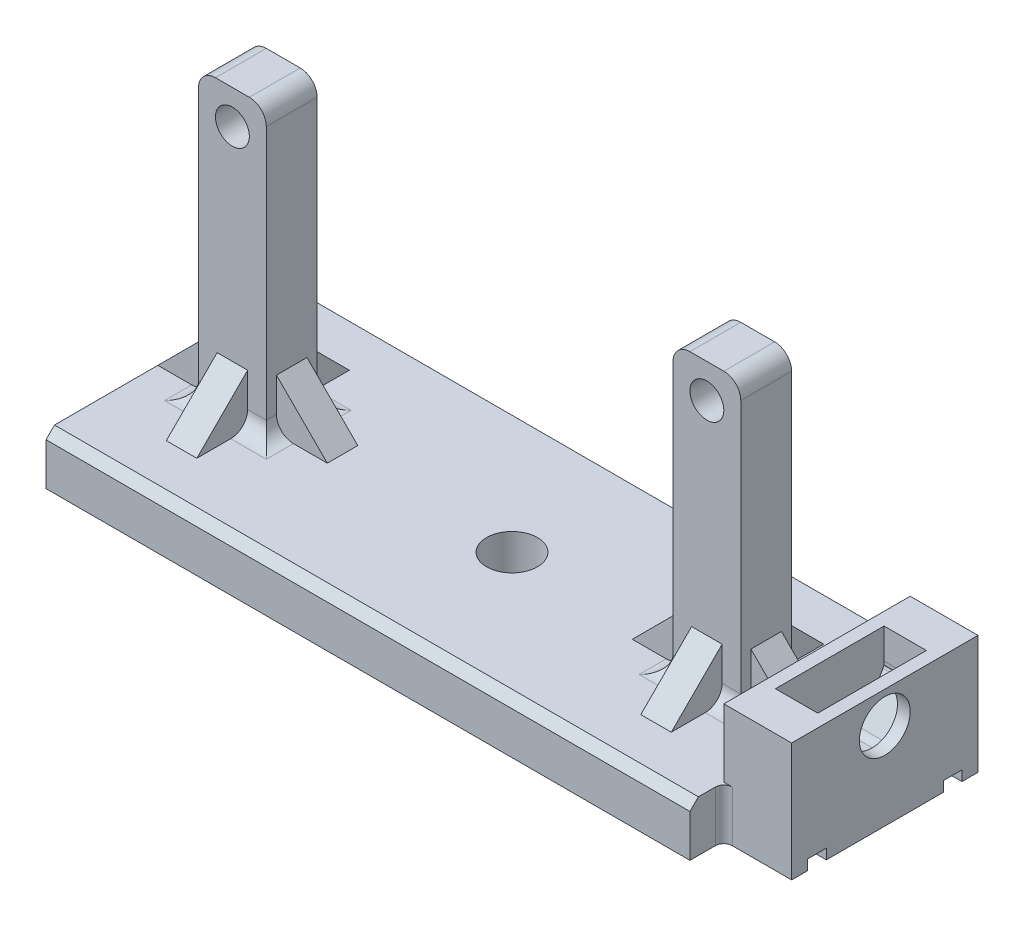
SolidWorks part; units mm, degrees
ref_plane "Alzado" through (0, 0, 0) normal (0, 0, 1) x (1, 0, 0)
ref_plane "Planta" through (0, 0, 0) normal (0, 1, 0) x (1, 0, 0)
ref_plane "Vista lateral" through (0, 0, 0) normal (1, 0, 0) x (0, 0, -1)
sketch "Croquis1" plane through (0, 0, 0) normal (0, 0, 1) x (1, 0, 0)
  line L0 (0, 0) -> (38, 0)
  line L1 (38, 0) -> (38, 3)
  line L2 (38, 3) -> (35, 3)
  line L3 (35, 3) -> (35, 20)
  line L4 (35, 20) -> (31, 20)
  line L5 (31, 20) -> (31, 3)
  line L6 (31, 3) -> (7, 3)
  line L7 (7, 3) -> (7, 20)
  line L8 (7, 20) -> (3, 20)
  line L9 (3, 20) -> (3, 3)
  line L10 (0, 0) -> (0, 3)
  line L11 (0, 3) -> (3, 3)
  circle A0 centre (5, 18) radius 1
  circle A1 centre (33, 18) radius 1
  point P19 (5, 20)
  point P21 (33, 20)
  dimension "D1" = 2
  dimension "D2" = 28
  dimension "D3" = 15
  dimension "D4" = 2
  dimension "D5" = 3
  dimension "D6" = 4
  dimension "D7" = 3
extrude "Saliente-Extruir1" add sketch "Croquis1" along normal mid plane 3
sketch "Croquis2" plane through (0, 0, 1.5) normal (0, 0, 1) x (1, 0, 0)
  line L1 (0, 3) -> (38, 3)
  line L2 (0, 3) -> (0, 0)
  line L3 (0, 0) -> (38, 0)
  line L4 (38, 3) -> (38, 0)
extrude "Saliente-Extruir2" add sketch "Croquis2" along normal blind 6
sketch "Croquis3" plane through (0, 0, -1.5) normal (0, 0, -1) x (-1, 0, 0)
  line L1 (-38, 3) -> (0, 3)
  line L2 (-38, 3) -> (-38, 0)
  line L3 (-38, 0) -> (0, 0)
  line L4 (0, 3) -> (0, 0)
extrude "Saliente-Extruir3" add sketch "Croquis3" along normal blind 6
fillet "Redondeo1" radius 1 4 edges at (35, 20, 0) (31, 20, 0) (7, 20, 0) (3, 20, 0)
sketch "Croquis4" plane through (0, 0, 0) normal (0, 0, 1) x (1, 0, 0)
  line L3 (35, 6) -> (38, 3)
  line L4 (35, 3) -> (35, 19) construction
  dimension "D2" = 3
  dimension "D4" = 3
rib "Nervio1" sketch "Croquis4" sketch "Croquis4" thickness 1.8 extrusion direction parallel to sketch draft on no parameters "D1"=1.8
sketch "Croquis5" plane through (0, 0, 0) normal (0, 0, 1) x (1, 0, 0)
  line L0 (31, 6) -> (28, 3)
  line L1 (31, 19) -> (31, 3) construction
  line L2 (38, 3) -> (0, 3) construction
  dimension "D1" = 3
  dimension "D2" = 3
rib "Nervio5" sketch "Croquis5" sketch "Croquis5" thickness 1.8 extrusion direction parallel to sketch draft on no parameters "D1"=1.8
ref_plane "Plano2" through (33, 0, 0) normal (1, 0, 0) x (0, 0, -1)
sketch "Croquis6" plane through (33, 0, 0) normal (1, 0, 0) x (0, 0, -1)
  line L0 (1.5, 6) -> (4.5, 3)
  line L1 (1.5, 3) -> (1.5, 19) construction
  line L2 (0.9, 3) -> (7.5, 3) construction
  dimension "D1" = 3
  dimension "D2" = 3
rib "Nervio6" sketch "Croquis6" sketch "Croquis6" thickness 1.8 extrusion direction parallel to sketch draft on no parameters "D1"=1.8
sketch "Croquis7" plane through (33, 0, 0) normal (1, 0, 0) x (0, 0, -1)
  line L0 (-1.5, 6) -> (-4.5, 3)
  line L1 (-1.5, 3) -> (-1.5, 19) construction
  line L2 (-7.5, 3) -> (-0.9, 3) construction
  dimension "D1" = 3
  dimension "D2" = 3
rib "Nervio7" sketch "Croquis7" sketch "Croquis7" thickness 1.8 extrusion direction parallel to sketch draft on no parameters "D1"=1.8
ref_plane "Plano1" through (19, 0, 0) normal (-1, 0, 0) x (0, 0, 1)
mirror "Simetría3" about plane through (19, 0, 0) normal (-1, 0, 0) of "Nervio1", "Nervio7", "Nervio6", "Nervio5"
fillet "Redondeo2" radius 1 16 edges at (31.55, 3, 1.5) (31, 3, 1.2) (34.45, 3, 1.5) (35, 3, 1.2) (35, 3, -1.2) (34.45, 3, -1.5) (31, 3, -1.2) (31.55, 3, -1.5) (3, 3, -1.2) (3.55, 3, -1.5) (6.45, 3, -1.5) (7, 3, -1.2) (7, 3, 1.2) (6.45, 3, 1.5) (3, 3, 1.2) (3.55, 3, 1.5)
sketch "Croquis8" plane through (0, 0, 0) normal (0, -1, 0) x (1, 0, 0)
  line L0 (0, 7.5) -> (0, -7.5) construction
  line L1 (0, 4.55) -> (38, 4.55)
  line L2 (0, 4.55) -> (0, 3.45)
  line L3 (0, 3.45) -> (38, 3.45)
  line L4 (38, 4.55) -> (38, 3.45)
  line L5 (38, 7.5) -> (38, -7.5) construction
  line L6 (0, 7.5) -> (38, 7.5) construction
  line L7 (0, -3.45) -> (38.2491, -3.45)
  line L8 (0, -3.45) -> (0, -4.55)
  line L9 (0, -4.55) -> (38.2491, -4.55)
  line L10 (38.2491, -3.45) -> (38.2491, -4.55)
  line L11 (38, -7.5) -> (0, -7.5) construction
  dimension "D1" = 2.95
  dimension "D2" = 2.95
  dimension "D3" = 1.1
  dimension "D4" = 1.1
extrude "Cortar-Extruir1" cut sketch "Croquis8" against normal blind 0.6
sketch "Croquis10" plane through (0, 3, 0) normal (0, 1, 0) x (1, 0, 0)
  line L0 (38, 0.9) -> (38, 7.5) construction
  line L1 (42, 5.5) -> (38, 5.5)
  line L2 (42, 5.5) -> (42, -5.5)
  line L3 (42, -5.5) -> (38, -5.5)
  line L4 (38, 5.5) -> (38, -5.5)
  point P4 (38, 0)
  dimension "D1" = 4
  dimension "D2" = 11
extrude "Saliente-Extruir5" add sketch "Croquis10" against normal up to surface (3 mm away) and the other way blind 4 from surface up to face at (19, 0, 0) starting at face at (19, 3, 0)
sketch "Croquis11" plane through (38, 0, 0) normal (-1, 0, 0) x (0, 0, 1)
  line L0 (7.5, 0) -> (-7.5, 0) construction
  line L1 (1.6454, 2.27) -> (3.2909, 5.12)
  line L2 (3.2909, 5.12) -> (1.6454, 7.97)
  line L3 (1.6454, 7.97) -> (-1.6454, 7.97)
  line L4 (-1.6454, 7.97) -> (-3.2909, 5.12)
  line L5 (-3.2909, 5.12) -> (-1.6454, 2.27)
  line L6 (-1.6454, 2.27) -> (1.6454, 2.27)
  circle A0 centre (0, 5.12) radius 2.85 construction
  circle A1 centre (0, 5.12) radius 1.5
  dimension "D1" = 5.7
  dimension "D3" = 3
  dimension "D2" = 5.12
extrude "Cortar-Extruir2" cut sketch "Croquis11" along normal mid plane 2.5 from offset 2 contours L4 L5 L6 L1 L2 L3 offset against normal yes
fillet "Redondeo5" radius 0.5 4 edges at (40, 5.12, -3.2909) (40, 2.27, -1.6454) (40, 5.12, 3.2909) (40, 2.27, 1.6454)
sketch "Croquis13" plane through (0, 0, 0) normal (0, -1, 0) x (1, 0, 0)
  line L0 (42, 5.5) -> (42, -5.5) construction
  line L1 (38, 4.55) -> (42, 4.55)
  line L2 (38, 4.55) -> (38, 3.45)
  line L3 (38, 3.45) -> (42, 3.45)
  line L4 (42, 4.55) -> (42, 3.45)
  line L5 (0, 3.45) -> (38, 3.45) construction
  line L6 (38, -3.45) -> (42, -3.45)
  line L7 (38, -3.45) -> (38, -4.55)
  line L8 (38, -4.55) -> (42, -4.55)
  line L9 (42, -3.45) -> (42, -4.55)
  line L10 (0, -4.55) -> (38, -4.55) construction
extrude "Cortar-Extruir4" cut sketch "Croquis13" against normal blind 0.6
sketch "Croquis14" plane through (0, 7, 0) normal (0, 1, 0) x (1, 0, 0)
  line L0 (38.75, 1.3568) -> (38.75, -1.3568) construction
  line L1 (38.75, 3.2055) -> (41.25, 3.2055)
  line L2 (38.75, 3.2055) -> (38.75, -3.2055)
  line L3 (38.75, -3.2055) -> (41.25, -3.2055)
  line L4 (41.25, 3.2055) -> (41.25, -3.2055)
  line L5 (41.25, 1.3568) -> (41.25, -1.3568) construction
  line L6 (41.25, -2.2055) -> (38.75, -2.2055) construction
  line L7 (38.75, 2.2055) -> (41.25, 2.2055) construction
  dimension "D1" = 1
  dimension "D2" = 1
extrude "Cortar-Extruir5" cut sketch "Croquis14" against normal blind 2
extrude "Cortar-Extruir6" cut sketch "Croquis11<3>" against normal blind 4 from surface contours A1 starting at face at (41.25, 4.605, 0)
sketch "Croquis11<3>" plane through (38, 0, 0) normal (-1, 0, 0) x (0, 0, 1) same geometry as "Croquis11"
sketch "Croquis16" plane through (0, 3, 0) normal (0, 1, 0) x (1, 0, 0)
  line L0 (0, 0.9) -> (0, 7.5) construction
  circle A0 centre (20, 0) radius 1.5
  dimension "D1" = 3
  dimension "D2" = 20
extrude "Cortar-Extruir7" cut sketch "Croquis16" against normal up to next
fillet "Redondeo6" radius 0.5 2 edges at (38, 1.5, -5.5) (38, 1.5, 5.5)
chamfer "Chaflán1" distance 0.5 angle 45 2 edges at (19, 3, -7.5) (19, 3, 7.5)
equation "\"h\"= 15"
equation "\"D3@Croquis1\"=\"h\""
